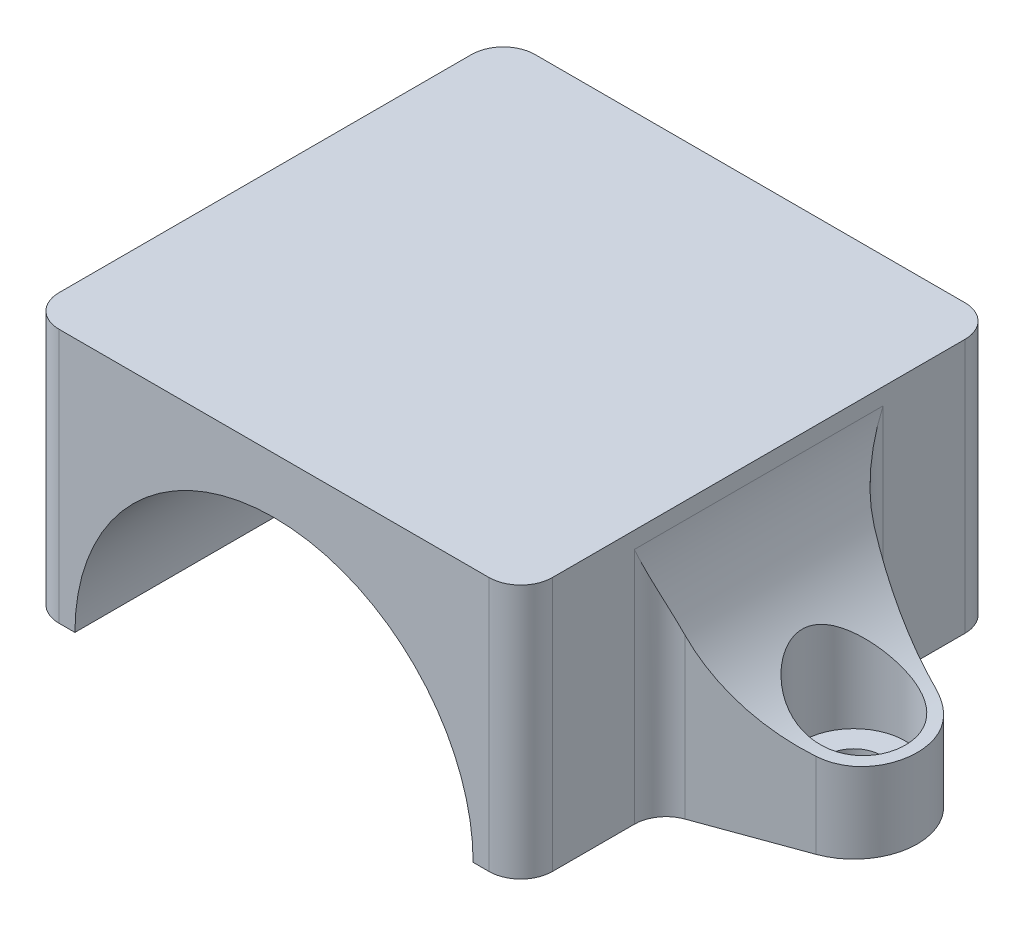
SolidWorks part; units mm, degrees
ref_plane "Front Plane" through (0, 0, 0) normal (0, 0, 1) x (1, 0, 0)
ref_plane "Top Plane" through (0, 0, 0) normal (0, 1, 0) x (1, 0, 0)
ref_plane "Right Plane" through (0, 0, 0) normal (1, 0, 0) x (0, 0, -1)
sketch "Sketch1" plane through (0, 0, 0) normal (0, 0, 1) x (1, 0, 0)
  line L0 (-15.55, 0) -> (-12.55, 0)
  line L1 (12.55, 0) -> (15.55, 0)
  line L2 (-15.55, 0) -> (-15.55, 16.05)
  line L3 (-15.55, 16.05) -> (15.55, 16.05)
  line L4 (15.55, 16.05) -> (15.55, 0)
  arc A0 (12.55, 0) -> (-12.55, 0) centre (0, 0) ccw
  arc A1 (15.55, 0) -> (-15.55, 0) centre (0, 0) ccw construction
  point P6 (0, 15.55)
  dimension "D2" = 3
  dimension "D3" = 0.5
  dimension "D1" = 25.1
extrude "Boss-Extrude2" add sketch "Sketch1" along normal mid plane 30
sketch "Sketch2" plane through (0, 0, 0) normal (0, 1, 0) x (1, 0, 0)
  line L0 (-15.55, 6.4405) -> (-15.55, -6.4405)
  line L1 (-15.55, -15) -> (-15.55, 15) construction
  line L2 (-15.55, -6.4405) -> (-22.9181, -3.7588)
  line L3 (-22.9181, 3.7588) -> (-15.55, 6.4405)
  line L4 (0, 0) -> (0, -50000) construction
  line L5 (22.9181, 3.7588) -> (15.55, 6.4405)
  line L6 (15.55, -6.4405) -> (22.9181, -3.7588)
  line L7 (15.55, 6.4405) -> (15.55, -6.4405)
  arc A0 (-22.9181, -3.7588) -> (-22.9181, 3.7588) centre (-21.55, 0) cw
  arc A1 (22.9181, -3.7588) -> (22.9181, 3.7588) centre (21.55, 0) ccw
  circle A2 centre (-21.55, 0) radius 2.5 construction
  point P5 (-15.55, 0)
  point P16 (15.55, 0)
  point P18 (-15.55, 7.7244)
  dimension "D1" = 5
  dimension "D2" = 4
  dimension "D3" = 40
  dimension "D4" = 6
extrude "Boss-Extrude3" add sketch "Sketch2" along normal blind 5
fillet "Fillet1" radius 2 8 edges at (-15.55, 2.5, -6.4405) (-15.55, 2.5, 6.4405) (15.55, 2.5, -6.4405) (15.55, 2.5, 6.4405) (15.55, 8.025, -15) (15.55, 8.025, 15) (-15.55, 8.025, -15) (-15.55, 8.025, 15)
sketch "Sketch3" plane through (0, 5, 0) normal (0, 1, 0) x (1, 0, 0)
  point P0 (-21.55, 0)
  point P1 (21.55, 0)
hole_wizard "CBORE for M3 SHCS1" positions "Sketch3" profile "Sketch4" counterbore size "M3" standard "ANSI Metric" end condition through all
sketch "Sketch4" plane through (-21.55, 5, 0) normal (1, 0, 0) x (0, 0, 1)
  line L0 (0, 0) -> (0, 5)
  line L1 (0, 5) -> (1.7, 5)
  line L3 (1.7, 5) -> (1.7, 3)
  line L4 (1.7, 3) -> (3.25, 3)
  line L5 (3.25, 3) -> (3.25, 0)
  line L7 (3.25, 0) -> (0, 0)
  line L11 (0, -6.35) -> (0, 107.95) construction
  dimension "Thru Hole Dia." = 3.4
  dimension "Thru Hole Depth" = 5
  dimension "C'Bore Dia." = 6.5
  dimension "C'Bore Depth" = 3
fillet "Fillet2" radius 10 2 edges at (15.55, 5, 0) (-15.55, 5, 0)
